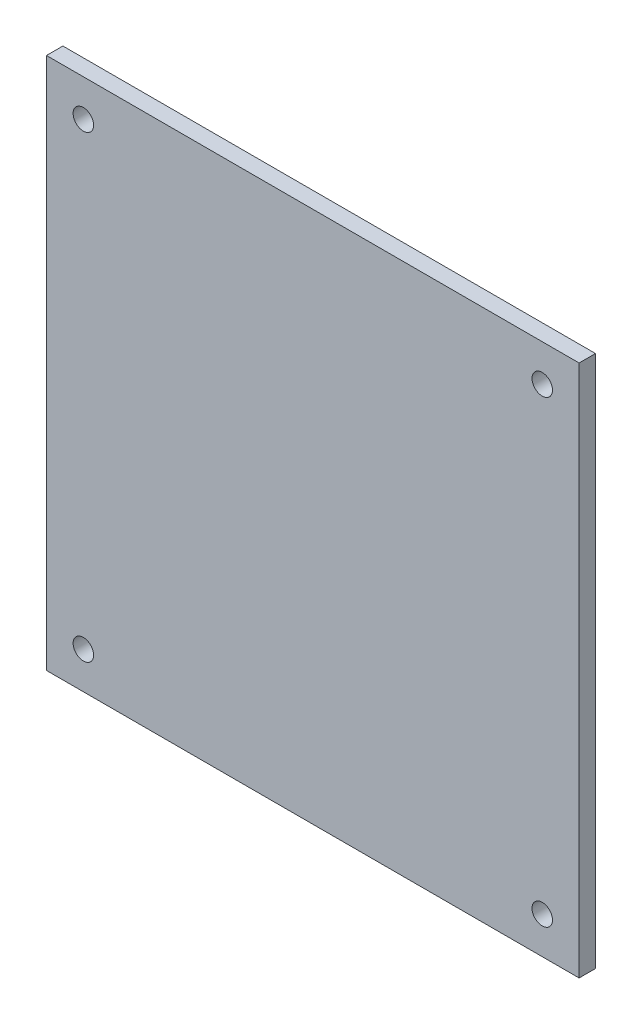
SolidWorks part; units mm, degrees
material "Aluminum"
ref_plane "Front Plane" through (0, 0, 0) normal (0, 0, 1) x (1, 0, 0)
ref_plane "Top Plane" through (0, 0, 0) normal (0, 1, 0) x (1, 0, 0)
ref_plane "Right Plane" through (0, 0, 0) normal (1, 0, 0) x (0, 0, -1)
sketch "Sketch1" plane through (0, 0, 0) normal (0, 0, 1) x (1, 0, 0)
  line L1 (65, -65) -> (-65, -65)
  line L2 (65, -65) -> (65, 65)
  line L3 (65, 65) -> (-65, 65)
  line L4 (-65, -65) -> (-65, 65)
  line L5 (65, -65) -> (-65, 65) construction
  line L6 (65, 65) -> (-65, -65) construction
  point P0 (0, 0)
  dimension "D1" = 130
  dimension "D2" = 130
extrude "Boss-Extrude1" add sketch "Sketch1" along normal blind 2 and the other way blind 2
hole_wizard "Tap Drill for M5x0.8 Tap1" positions "Sketch3" profile "Sketch2" hole size "M5x0.8" standard "ANSI Metric" end condition through all
sketch "Sketch3" plane through (0, 0, -2) normal (0, 0, -1) x (-1, 0, 0)
  point P0 (-56, 56)
  point P3 (56, 56)
  point P6 (56, -56)
  point P9 (-56, -56)
sketch "Sketch2" plane through (56, 56, -2) normal (1, 0, 0) x (0, 1, 0)
  line L0 (0, 0) -> (0, 4)
  line L1 (0, 4) -> (2.5, 4)
  line L2 (2.5, 4) -> (2.5, 0)
  line L5 (2.5, 0) -> (0, 0)
  line L11 (0, -6.35) -> (0, 107.95) construction
  dimension "Thru Hole Dia." = 5
  dimension "Thru Hole Depth" = 4
